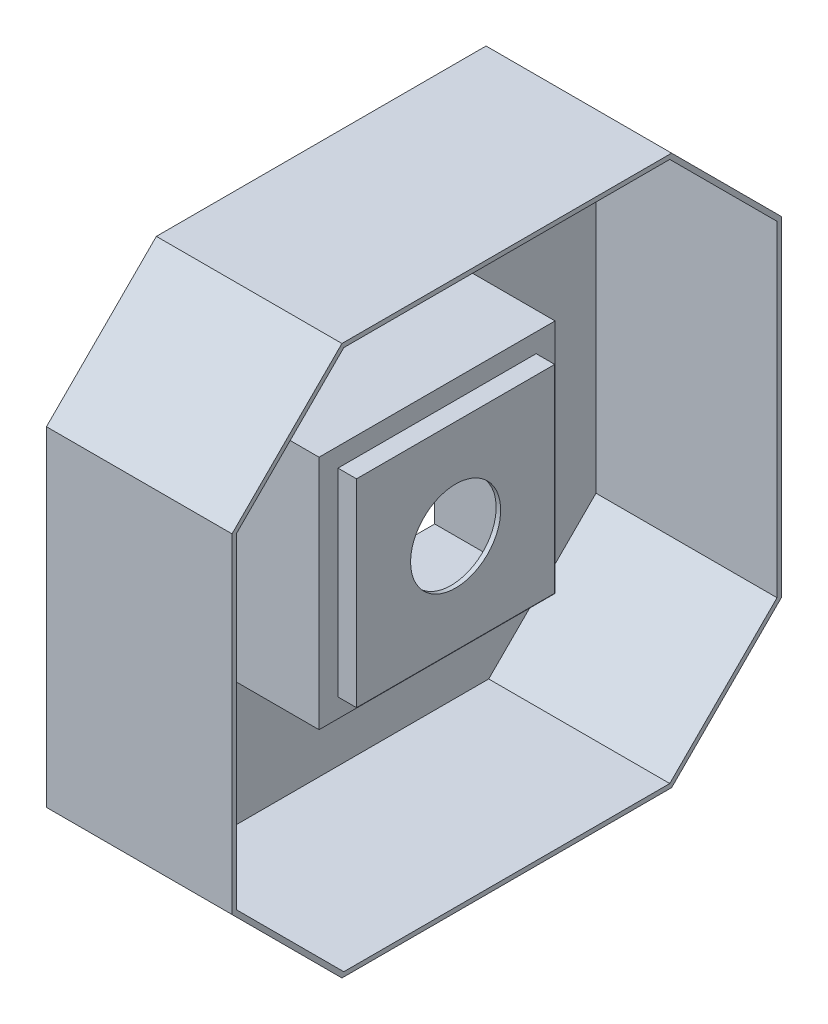
SolidWorks part; units mm, degrees
ref_plane "前视基准面" through (0, 0, 0) normal (0, 0, 1) x (1, 0, 0)
ref_plane "上视基准面" through (0, 0, 0) normal (0, 1, 0) x (1, 0, 0)
ref_plane "右视基准面" through (0, 0, 0) normal (1, 0, 0) x (0, 0, -1)
sketch "草图2" plane through (0, 0, 0) normal (1, 0, 0) x (0, 0, -1)
  line L0 (-183, 305) -> (-305, 183)
  line L1 (-183, 305) -> (183, 305)
  line L2 (-305, 183) -> (-305, -183)
  line L3 (-183, -305) -> (183, -305)
  line L4 (305, 183) -> (305, -183)
  line L5 (-305, 305) -> (305, -305) construction
  line L6 (-305, -305) -> (305, 305) construction
  line L7 (183, 305) -> (305, 183)
  line L8 (183, -305) -> (305, -183)
  line L9 (-305, -183) -> (-183, -305)
  point P0 (0, 0)
  dimension "D1" = 610
  dimension "D2" = 610
extrude "凸台-拉伸1" add sketch "草图2" along normal blind 206
sketch "草图5" plane through (0, 0, 0) normal (1, 0, 0) x (0, 0, -1)
  line L1 (-126, 126) -> (126, 126)
  line L2 (-126, 126) -> (-126, -126)
  line L3 (-126, -126) -> (126, -126)
  line L4 (126, 126) -> (126, -126)
  line L5 (-126, 126) -> (126, -126) construction
  line L6 (-126, -126) -> (126, 126) construction
  point P0 (0, 0)
  dimension "D1" = 252
  dimension "D2" = 252
extrude "切除-拉伸1" cut sketch "草图5" along normal blind 123.6
sketch "草图6" plane through (0, 0, 0) normal (-1, 0, 0) x (0, 0, 1)
  line L1 (-105, 105) -> (105, 105)
  line L2 (-105, 105) -> (-105, -105)
  line L3 (-105, -105) -> (105, -105)
  line L4 (105, 105) -> (105, -105)
  line L5 (-105, 105) -> (105, -105) construction
  line L6 (-105, -105) -> (105, 105) construction
  point P0 (0, 0)
  dimension "D1" = 210
  dimension "D2" = 210
extrude "切除-拉伸2" cut sketch "草图6" against normal blind 144.2
shell "抽壳1" thickness 5 removed face at (206, 0, 0)
sketch "草图7" plane through (144.2, 0, 0) normal (-1, 0, 0) x (0, 0, 1)
  circle A0 centre (0, 0) radius 50
  dimension "D1" = 100
extrude "切除-拉伸3" cut sketch "草图7" against normal through all
